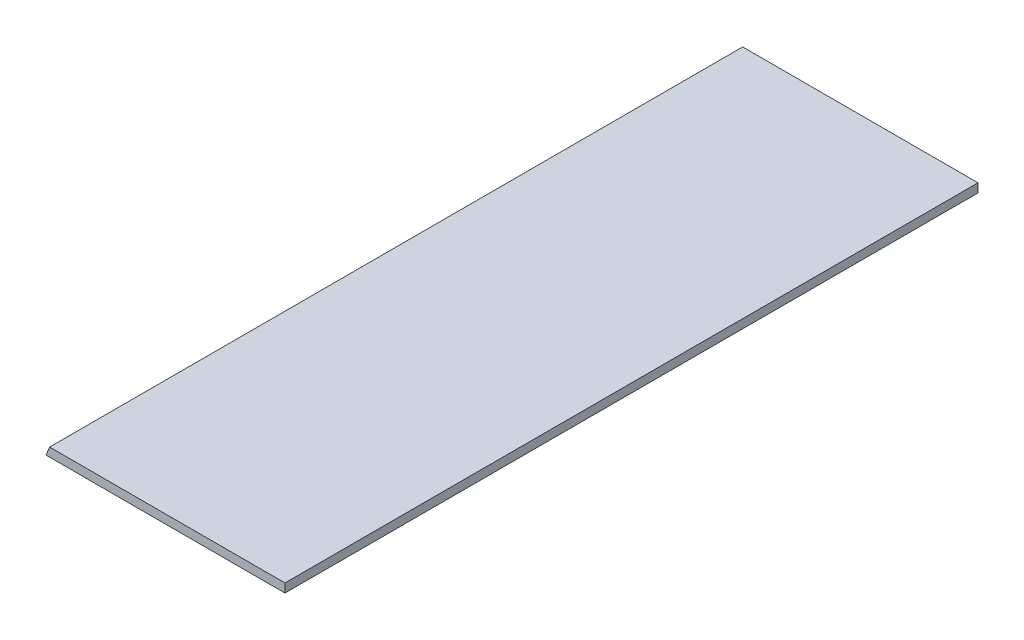
SolidWorks part; units mm, degrees
ref_plane "Front Plane" through (0, 0, 0) normal (0, 0, 1) x (1, 0, 0)
ref_plane "Top Plane" through (0, 0, 0) normal (0, 1, 0) x (1, 0, 0)
ref_plane "Right Plane" through (0, 0, 0) normal (1, 0, 0) x (0, 0, -1)
sketch "Sketch1" plane through (0, 0, 0) normal (0, 0, 1) x (1, 0, 0)
  line L0 (0, 0) -> (2.6303, 6.35)
  line L1 (2.6303, 6.35) -> (172.974, 6.35)
  line L2 (172.974, 6.35) -> (172.974, 0)
  line L3 (172.974, 0) -> (0, 0)
  dimension "D1" = 67.5
  dimension "D2" = 6.35
  dimension "D3" = 172.974
extrude "Boss-Extrude1" add sketch "Sketch1" along normal blind 501.65
